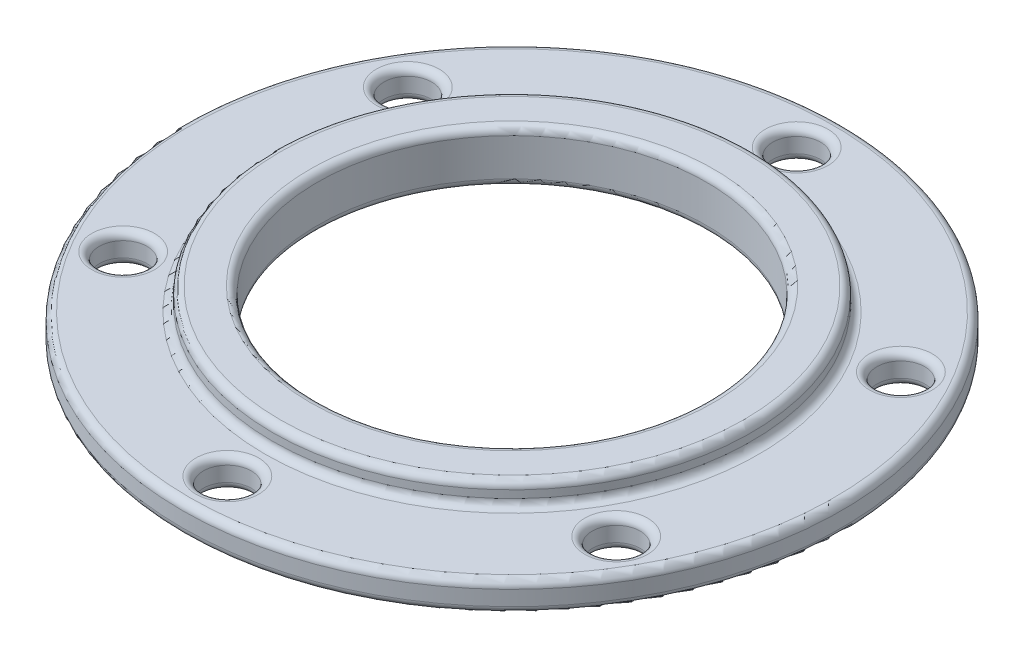
SolidWorks part; units mm, degrees
ref_plane "Front Plane" through (0, 0, 0) normal (0, 0, 1) x (1, 0, 0)
ref_plane "Top Plane" through (0, 0, 0) normal (0, 1, 0) x (1, 0, 0)
ref_plane "Right Plane" through (0, 0, 0) normal (1, 0, 0) x (0, 0, -1)
sketch "Sketch1" plane through (0, 0, 0) normal (0, 1, 0) x (1, 0, 0)
  circle A0 centre (0, 0) radius 22.025
  arc A1 (-0.6528, -22.0153) -> (-0.6528, 22.0153) centre (0, 0) ccw construction
  circle A2 centre (0, 19.025) radius 1.6
  circle A3 centre (16.4761, 9.5125) radius 1.6
  circle A4 centre (16.4761, -9.5125) radius 1.6
  circle A5 centre (0, -19.025) radius 1.6
  circle A6 centre (-16.4761, -9.5125) radius 1.6
  circle A7 centre (-16.4761, 9.5125) radius 1.6
  circle A8 centre (0, 0) radius 13
  point P21 (0, 0)
  dimension "D1" = 3.2
  dimension "D3" = 26
  dimension "D4" = 44.05
  dimension "D2" = 6
extrude "Boss-Extrude1" add sketch "Sketch1" against normal blind 2
ref_axis "Axis1" through (0, -2.175, 0) along (0, 1, 0)
sketch "Sketch2" plane through (0, 0, 0) normal (0, 1, 0) x (1, 0, 0)
  circle A0 centre (0, 0) radius 13
  circle A1 centre (0, 0) radius 16
  dimension "D1" = 26
  dimension "D2" = 32
extrude "Boss-Extrude2" add sketch "Sketch2" along normal blind 1.5
fillet "Fillet1" radius 0.5 18 edges at (0, 0, 22.025) (0, 0, -17.425) (16.4761, 0, -7.9125) (16.4761, 0, 11.1125) (0, 0, 20.625) (-16.4761, 0, 11.1125) (-16.4761, 0, -7.9125) (0, -2, 22.025) (0, -2, -17.425) (0, -2, 13) (16.4761, -2, -7.9125) (16.4761, -2, 11.1125) (0, -2, 20.625) (-16.4761, -2, 11.1125) (-16.4761, -2, -7.9125) (0, 0, 16) (0, 1.5, 13) (0, 1.5, 16)
